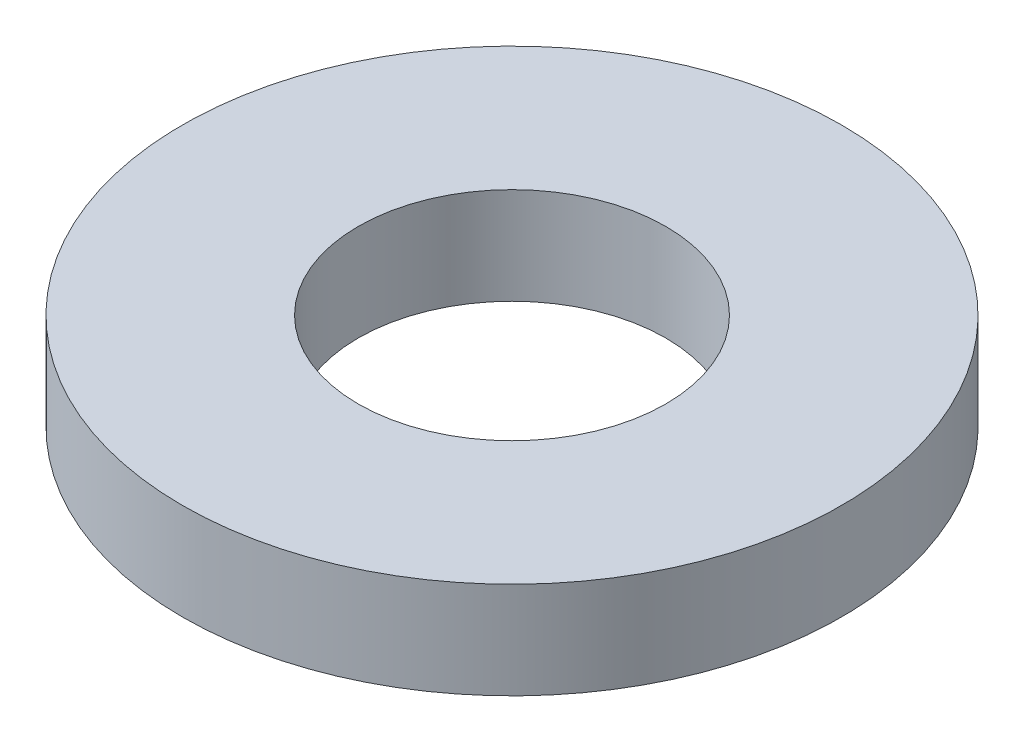
SolidWorks part; units mm, degrees
ref_plane "Front Plane" through (0, 0, 0) normal (0, 0, 1) x (1, 0, 0)
ref_plane "Top Plane" through (0, 0, 0) normal (0, 1, 0) x (1, 0, 0)
ref_plane "Right Plane" through (0, 0, 0) normal (1, 0, 0) x (0, 0, -1)
sketch "Sketch1" plane through (0, 0, 0) normal (0, 1, 0) x (1, 0, 0)
  circle A0 centre (0, 0) radius 75
  dimension "FLANGE_OD" = 150
extrude "Boss-Extrude1" add sketch "Sketch1" along normal blind 22
sketch "Sketch2" plane through (0, 0, 0) normal (0, 1, 0) x (1, 0, 0)
  circle A0 centre (0, 0) radius 35
  dimension "BORE_D" = 70
extrude "Cut-Extrude1" cut sketch "Sketch2" along normal through all
sketch "Sketch3" plane through (0, 22, 0) normal (0, 1, 0) x (1, 0, 0)
  circle A0 centre (0, 0) radius 21.1164 construction
  circle A1 centre (-21.1164, 0) radius 2.0042
  dimension "BOLT_D" = 4.0085
  dimension "BOLT_PCD" = 42.2327
extrude "Cut-Extrude2" cut sketch "Sketch3" against normal blind 14.3301 rebuild error yes
pattern_circular "CirPattern1" count 3 over 360 rebuild error yes
